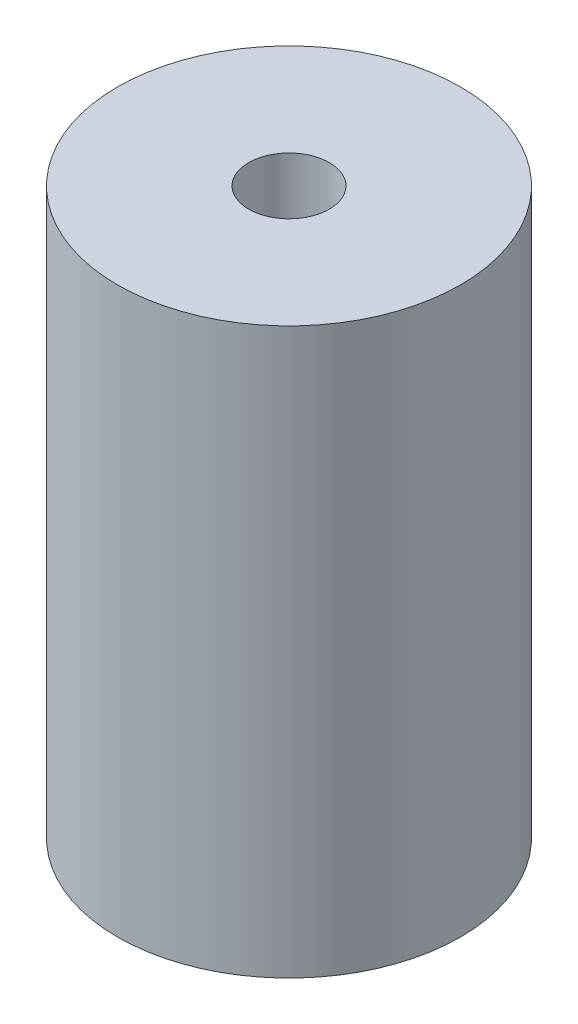
SolidWorks part; units mm, degrees
material "Rubber"
ref_plane "Front Plane" through (0, 0, 0) normal (0, 0, 1) x (1, 0, 0)
ref_plane "Top Plane" through (0, 0, 0) normal (0, 1, 0) x (1, 0, 0)
ref_plane "Right Plane" through (0, 0, 0) normal (1, 0, 0) x (0, 0, -1)
sketch "Sketch1" plane through (0, 0, 0) normal (0, 1, 0) x (1, 0, 0)
  circle A0 centre (0, 0) radius 6.35
  circle A1 centre (0, 0) radius 26.9875
extrude "Boss-Extrude1" add sketch "Sketch1" along normal blind 88.9
